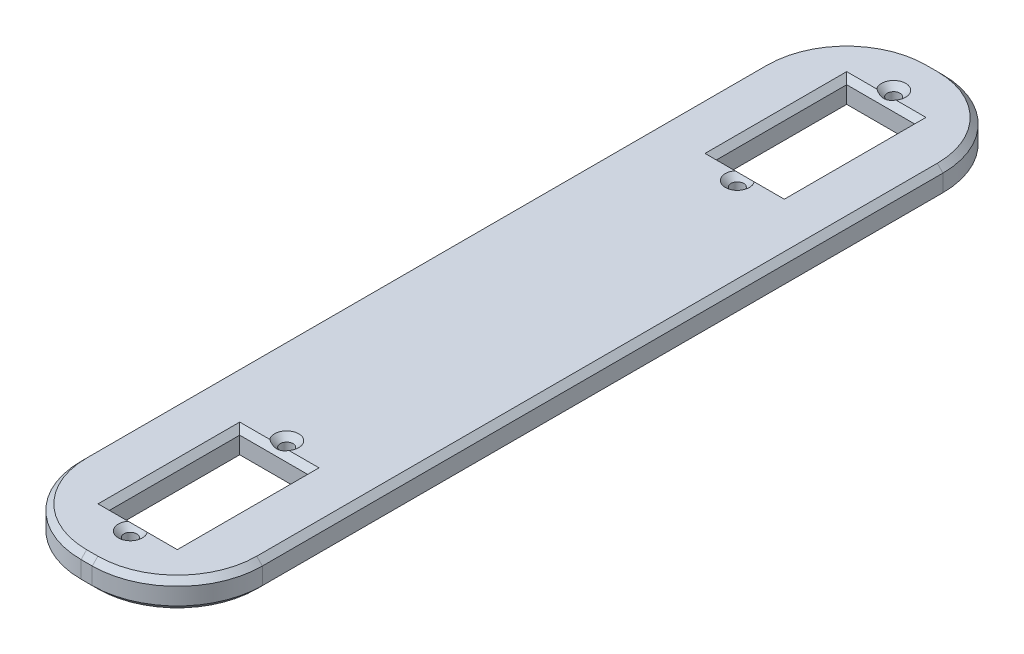
SolidWorks part; units mm, degrees
ref_plane "Front Plane" through (0, 0, 0) normal (0, 0, 1) x (1, 0, 0)
ref_plane "Top Plane" through (0, 0, 0) normal (0, 1, 0) x (1, 0, 0)
ref_plane "Right Plane" through (0, 0, 0) normal (1, 0, 0) x (0, 0, -1)
sketch "Sketch3" plane through (0, 0, 0) normal (0, 1, 0) x (1, 0, 0)
  line L0 (-5.99, -65) -> (5.99, -42.02) construction
  line L1 (-15.99, 0) -> (15.99, 0)
  line L2 (-15.99, -75) -> (-15.99, 75)
  line L3 (-15.99, 75) -> (15.99, 75)
  line L4 (15.99, -75) -> (15.99, 75)
  line L5 (-15.99, 0) -> (15.99, 75) construction
  line L6 (-15.99, 75) -> (15.99, 0) construction
  line L7 (-5.99, 42.02) -> (5.99, 42.02)
  line L8 (-5.99, 42.02) -> (-5.99, 65)
  line L9 (-5.99, 65) -> (5.99, 65)
  line L10 (5.99, 42.02) -> (5.99, 65)
  line L11 (-5.99, 42.02) -> (5.99, 65) construction
  line L12 (-5.99, 65) -> (5.99, 42.02) construction
  line L13 (-5.99, -42.02) -> (5.99, -65) construction
  line L14 (-15.99, -75) -> (15.99, 0) construction
  line L15 (-15.99, 0) -> (15.99, -75) construction
  line L16 (5.99, -42.02) -> (5.99, -65)
  line L17 (-5.99, -65) -> (5.99, -65)
  line L18 (-5.99, -42.02) -> (-5.99, -65)
  line L19 (-5.99, -42.02) -> (5.99, -42.02)
  line L20 (-15.99, -75) -> (15.99, -75)
  line L21 (-5.99, 53.51) -> (5.99, 53.51) construction
  circle A0 centre (0, 67.29) radius 1.125
  circle A1 centre (0, 39.73) radius 1.125
  circle A2 centre (0, -67.29) radius 1.125
  circle A3 centre (0, -39.73) radius 1.125
  point P0 (0, 37.5)
  point P5 (0, 53.51)
  point P20 (0, -53.51)
  point P21 (0, -37.5)
  dimension "D6" = 2.25
  dimension "D1" = 11.98
  dimension "D2" = 10
  dimension "D3" = 10
  dimension "D4" = 22.98
  dimension "D5" = 75
  dimension "D7" = 2.29
extrude "Boss-Extrude1" add sketch "Sketch3" along normal blind 5 contours L1 L4 L3 L2 L10 L7 L8 L9 | L2 L20 L4 L1 L18 L19 L16 L17 region at (0, 0, -35.3561) region at (0, 0, 35.3561)
fillet "Fillet1" radius 15 4 edges at (-15.99, 2.5, -75) (15.99, 2.5, -75) (-15.99, 2.5, 75) (15.99, 2.5, 75)
chamfer "Chamfer1" distance 1 angle 45 40 edges at (0, 5, 68.415) (0, 5, 65) (5.99, 5, 53.51) (0, 5, 42.02) (-5.99, 5, 53.51) (0, 5, 40.855) (0, 5, -38.605) (0, 5, -66.165) (0, 5, -65) (-5.99, 5, -53.51) (0, 5, -42.02) (5.99, 5, -53.51) (11.5966, 5, -70.6066) (15.99, 5, 0) (11.5966, 5, 70.6066) (0, 5, 75) (-11.5966, 5, 70.6066) (-15.99, 5, 0) (-11.5966, 5, -70.6066) (0, 5, -75) (0, 0, 68.415) (0, 0, 42.02) (5.99, 0, 53.51) (0, 0, 65) (-5.99, 0, 53.51) (0, 0, 40.855) (0, 0, -38.605) (0, 0, -66.165) (0, 0, -42.02) (-5.99, 0, -53.51) (0, 0, -65) (5.99, 0, -53.51) (-11.5966, 0, 70.6066) (0, 0, 75) (11.5966, 0, 70.6066) (15.99, 0, 0) (11.5966, 0, -70.6066) (0, 0, -75) (-11.5966, 0, -70.6066) (-15.99, 0, 0)
